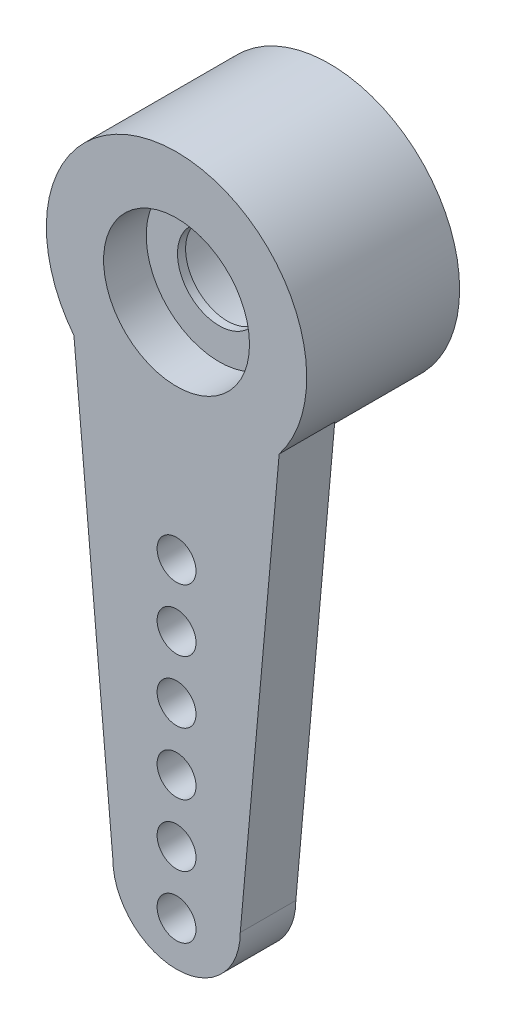
SolidWorks part; units mm, degrees
material "Nylon 6/10"
ref_plane "Front Plane" through (0, 0, 0) normal (0, 0, 1) x (1, 0, 0)
ref_plane "Top Plane" through (0, 0, 0) normal (0, 1, 0) x (1, 0, 0)
ref_plane "Right Plane" through (0, 0, 0) normal (1, 0, 0) x (0, 0, -1)
ref_plane "Plane1" through (0, 0, -7.033) normal (0, 0, 1) x (1, 0, 0)
sketch "Sketch1" plane through (0, 0, -7.033) normal (0, 0, 1) x (1, 0, 0)
  circle A0 centre (-5.5, 0) radius 3.5687
  circle A1 centre (-5.5, 0) radius 2
  dimension "D1" = 7.1374
extrude "Boss-Extrude1" add sketch "Sketch1" along normal blind 4.191
sketch "Sketch5" plane through (0, 0, -4.233) normal (0, 0, 1) x (1, 0, 0)
  circle A0 centre (-5.5, 0) radius 1.143
  circle A1 centre (-5.5, 0) radius 2 construction
  circle A2 centre (-5.5, 0) radius 2
  dimension "D1" = 2.286
extrude "Boss-Extrude2" add sketch "Sketch5" along normal offset from surface (0.2226 mm away) 1.1684 up to face at (-1.9313, 0, -2.842)
sketch "Sketch6" plane through (0, 0, -2.842) normal (0, 0, 1) x (1, 0, 0)
  line L0 (-3.7537, -14.0907) -> (-2.6869, -2.196)
  line L1 (-7.2462, -14.0907) -> (-8.313, -2.196)
  line L2 (-5.5, 0) -> (-5.5, -14.0907) construction
  line L3 (-5.5, -14.6241) -> (-5.5, -12.9223) construction
  arc A0 (-7.2462, -14.0907) -> (-3.7537, -14.0907) centre (-5.5, -14.0907) ccw
  circle A1 centre (-5.5, 0) radius 3.5687 construction
  circle A2 centre (-5.5, 0) radius 3.5687 construction
  circle A3 centre (-5.5, -12.9223) radius 0.5334
  circle A4 centre (-5.5, -14.6241) radius 0.5334
  circle A5 centre (-5.5, -11.2205) radius 0.5334
  circle A6 centre (-5.5, -9.5186) radius 0.5334
  circle A7 centre (-5.5, -7.8169) radius 0.5334
  circle A8 centre (-5.5, -6.1151) radius 0.5334
  arc A9 (-2.6869, -2.196) -> (-8.313, -2.196) centre (-5.5, 0) cw
  point P11 (-4.4823, -13.2601)
  dimension "D1" = 3.4925
  dimension "D2" = 15.8369
  dimension "D4" = 1.0668
  dimension "D3" = 5.6261
  dimension "D6" = 1.7018
  dimension "D5" = 6
extrude "Boss-Extrude3" add sketch "Sketch6" against normal blind 1.524
